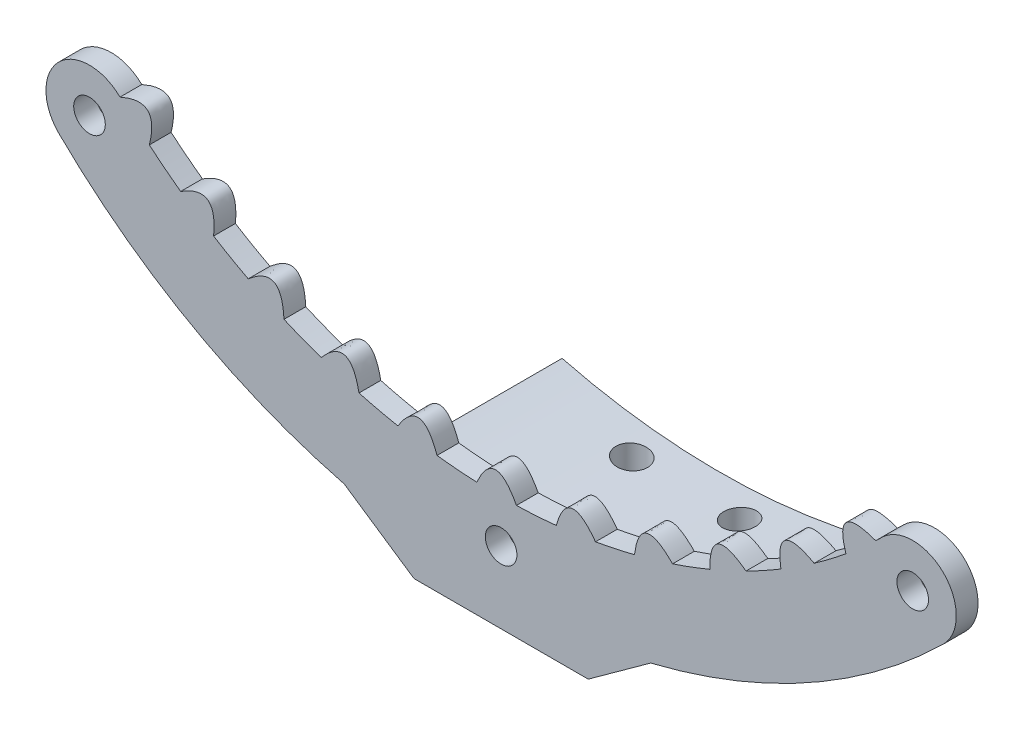
SolidWorks part; units mm, degrees
ref_plane "前视基准面" through (0, 0, 0) normal (0, 0, 1) x (1, 0, 0)
ref_plane "上视基准面" through (0, 0, 0) normal (0, 1, 0) x (1, 0, 0)
ref_plane "右视基准面" through (0, 0, 0) normal (1, 0, 0) x (0, 0, -1)
other "Configuration Table"
sketch "草图1" plane through (0, 0, 0) normal (0, 0, 1) x (1, 0, 0)
  line L0 (0, 0) -> (0, -35.7077) construction
  line L1 (-34.9994, -35.7077) -> (34.9994, -35.7077)
  line L2 (0, 0) -> (-34.9994, -35.7077)
  line L3 (-34.9994, -35.7077) -> (-40.5993, -41.421) construction
  line L4 (0, 0) -> (34.9994, -35.7077)
  line L5 (34.9994, -35.7077) -> (40.5993, -41.421) construction
  circle A0 centre (0, 0) radius 50
  circle A1 centre (0, 0) radius 58
  arc A2 (-34.9994, -35.7077) -> (-40.5993, -41.421) centre (-37.7994, -38.5643) ccw
  arc A3 (34.9994, -35.7077) -> (40.5993, -41.421) centre (37.7994, -38.5643) cw
  point P7 (0, -35.7077)
  dimension "D1" = 100
  dimension "D2" = 116
extrude "凸台-拉伸1" add sketch "草图1" along normal blind 2 contours A0 A1 region at (0, -50.8682, 0)
sketch "草图2" plane through (0, 0, 2) normal (0, 0, 1) x (1, 0, 0)
  arc A3 (-34.9994, -35.7077) -> (34.9994, -35.7077) centre (0, 0) ccw construction
  arc A4 (-34.9994, -35.7077) -> (35.0319, -35.6758) centre (0, 0) ccw
  spline S0 degree 2 poles (-34.9994, -35.7077) (-31.293, -34.0515) (-32.3048, -38.1628) knots 0 0 0 1 1 1
  spline S33 degree 2 poles (31.6656, -38.6948) (30.4246, -34.8296) (34.4007, -36.2849) knots 0 0 0 1 1 1
  spline S34 degree 2 poles (25.6941, -42.893) (25.0292, -38.8883) (28.751, -40.907) knots 0 0 0 1 1 1
  spline S35 degree 2 poles (19.175, -46.177) (19.1003, -42.1181) (22.4885, -44.6572) knots 0 0 0 1 1 1
  spline S36 degree 2 poles (12.2473, -48.4768) (12.7643, -44.4503) (15.7467, -47.4557) knots 0 0 0 1 1 1
  spline S37 degree 2 poles (5.0585, -49.7435) (6.1563, -45.8351) (8.6693, -49.2427) knots 0 0 0 1 1 1
  spline S38 degree 2 poles (-2.2381, -49.9499) (-0.583, -46.243) (1.4071, -49.9802) knots 0 0 0 1 1 1
  spline S39 degree 2 poles (-9.487, -49.0917) (-7.3098, -45.6653) (-5.8851, -49.6524) knots 0 0 0 1 1 1
  spline S40 degree 2 poles (-16.5338, -47.1872) (-13.8809, -44.1144) (-13.0518, -48.2664) knots 0 0 0 1 1 1
  spline S41 degree 2 poles (-23.2281, -44.277) (-20.156, -41.6232) (-19.9404, -45.8517) knots 0 0 0 1 1 1
  spline S42 degree 2 poles (-29.4273, -40.4232) (-26.0016, -38.2449) (-26.404, -42.4598) knots 0 0 0 1 1 1
extrude "凸台-拉伸6" add sketch "草图2" against normal blind 2 contours S0 A4 | S42 A4 | S41 A4 | S40 A4 | S39 A4 | S38 A4 | S37 A4 | S33 A4 | S34 A4 | S35 A4 | S36 A4 region at (-33.1887, -36.3688, 2) region at (32.5207, -36.9673, 2) region at (26.7917, -41.3084, 2) region at (20.4916, -44.7691, 2) region at (13.7548, -47.2756, 2) region at (6.7249, -48.7746, 2) region at (-0.4484, -49.2339, 2) region at (-7.6122, -48.644, 2) region at (-14.6137, -47.0173, 2) region at (-21.3037, -44.3884, 2) region at (-27.5397, -40.8136, 2)
sketch "草图3" plane through (0, 0, 2) normal (0, 0, 1) x (1, 0, 0)
  line L0 (-40.5993, -41.421) -> (40.5993, -41.421) construction
  line L1 (0, -41.421) -> (0, -58) construction
  arc A0 (-34.9994, -35.7077) -> (-40.5993, -41.421) centre (-37.7994, -38.5643) ccw construction
  arc A1 (-34.9994, -35.7077) -> (-40.5993, -41.421) centre (-37.7994, -38.5643) ccw
  circle A2 centre (-37.7994, -38.5643) radius 1.45
  arc A3 (40.5993, -41.421) -> (34.9994, -35.7077) centre (37.7994, -38.5643) ccw construction
  arc A4 (40.5993, -41.421) -> (34.9994, -35.7077) centre (37.7994, -38.5643) ccw
  circle A5 centre (37.7994, -38.5643) radius 1.45
  circle A6 centre (0, -53.9004) radius 1.45
  arc A7 (-40.5993, -41.421) -> (40.5993, -41.421) centre (0, 0) ccw construction
  arc A8 (-40.5993, -41.421) -> (40.5993, -41.421) centre (0, 0) ccw
  dimension "D1" = 2.9
  dimension "D2" = 2.9
  dimension "D3" = 2.9
extrude "切除-拉伸1" cut sketch "草图3" against normal blind 2 contours A2 | A6 | A5 region at (-37.7994, -38.5643, 2) region at (37.7994, -38.5643, 2) region at (0, -53.9004, 2)
sketch "草图5" plane through (0, 0, 2) normal (0, 0, 1) x (1, 0, 0)
  line L0 (-40.5993, -41.421) -> (40.5993, -41.421) construction
  line L1 (0, -41.421) -> (0, -58) construction
  line L2 (32.1195, -49.2313) -> (32.1784, -49.2313)
  line L3 (-8, -57.9999) -> (8, -57.9999)
  line L4 (-8, -57.4456) -> (-8, -60.4999)
  line L5 (-8, -60.4999) -> (8, -60.4999)
  line L6 (8, -60.4999) -> (8, -57.4456)
  line L7 (-8, -60.4999) -> (-14.4004, -56.1839)
  line L8 (8, -60.4999) -> (13.7387, -56.3493)
  arc A0 (-40.5993, -41.421) -> (40.5993, -41.421) centre (0, 0) ccw construction
  point P15 (0, -57.9999)
  arc M33 (-40.5993, -41.421) -> (40.5993, -41.421) centre (0, 0) ccw
  dimension "D1" = 8
  dimension "D2" = 8
  dimension "D3" = 2.5
extrude "凸台-拉伸7" add sketch "草图5" against normal blind 20 contours L4 L3 M33 | L3 L6 M33 | L5 L6 L3 L4 | L7 L4 M33 | L6 L8 M33 region at (-6.0019, -57.8338, 2) region at (-10.0877, -58.0939, 2) region at (0, -59.2499, 2) region at (6.0029, -57.8337, 2) region at (9.8804, -58.1379, 2)
sketch "草图6" plane through (0, -60.4999, 0) normal (0, -1, 0) x (1, 0, 0)
  line L0 (-7.9996, -9.9997) -> (7.9996, -9.9997) construction
  line L1 (0, 2) -> (0, -18) construction
  line L2 (-4.9497, -5.05) -> (4.9497, -5.05) construction
  line L3 (-4.9497, -5.05) -> (-4.9497, -14.9495) construction
  line L12 (-4.9497, -14.9495) -> (4.9497, -14.9495) construction
  line L13 (4.9497, -5.05) -> (4.9497, -14.9495) construction
  line L14 (-4.9497, -5.05) -> (4.9497, -14.9495) construction
  line L15 (-4.9497, -14.9495) -> (4.9497, -5.05) construction
  line L16 (0, -18) -> (0, -1.9995)
  circle A0 centre (-4.9497, -5.05) radius 1.45
  circle A1 centre (-4.9497, -14.9495) radius 1.45
  circle A2 centre (4.9497, -14.9495) radius 1.45
  circle A3 centre (4.9497, -5.05) radius 1.45
  point P5 (-4.9497, -14.6505)
  point P6 (0, -9.9997)
  dimension "D3" = 2.9
  dimension "D1" = 9.8995
extrude "切除-拉伸2" cut sketch "草图6" against normal blind 20 contours A1 | A0 | A2 | A3
